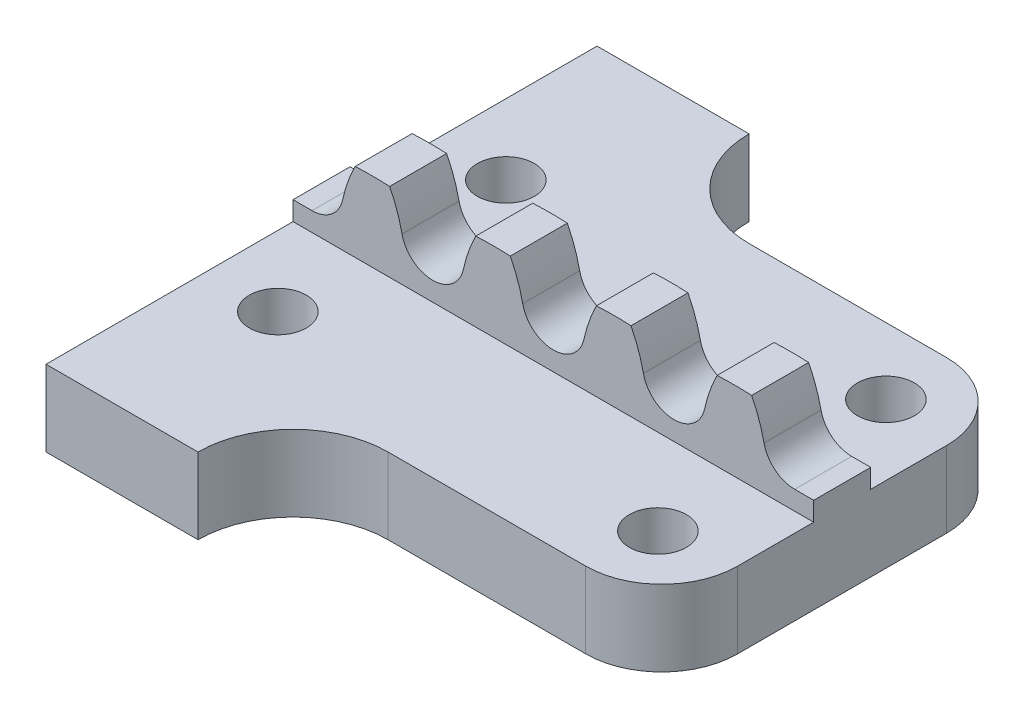
SolidWorks part; units mm, degrees
material "合金钢"
ref_plane "前视基准面" through (0, 0, 0) normal (0, 0, 1) x (1, 0, 0)
ref_plane "上视基准面" through (0, 0, 0) normal (0, 1, 0) x (1, 0, 0)
ref_plane "右视基准面" through (0, 0, 0) normal (1, 0, 0) x (0, 0, -1)
sketch "草图1" plane through (0, 0, 0) normal (0, 0, 1) x (1, 0, 0)
  line L0 (-0.6404, -1.8816) -> (-1.6404, -1.8816)
  line L1 (24.7596, -1.8816) -> (25.7596, -1.8816)
  line L2 (-1.6404, -1.8816) -> (-1.6404, -2.8816)
  line L3 (-1.6404, -2.8816) -> (25.7596, -2.8816)
  line L4 (25.7596, -2.8816) -> (25.7596, -1.8816)
  line L5 (-1.6404, -2.8816) -> (-1.6404, -6.8816)
  line L6 (-1.6404, -6.8816) -> (25.7596, -6.8816)
  line L7 (25.7596, -6.8816) -> (25.7596, -1.8816)
  arc A0 (4.0971, -0.5771) -> (3.4439, 1.2653) centre (-3.2619, -2.1492) ccw
  arc A1 (4.0971, -0.5771) -> (5.4066, -1.8535) centre (5.7096, -0.2326) ccw
  arc A2 (0.9722, -0.5771) -> (1.6254, 1.2653) centre (8.3312, -2.1492) cw
  arc A3 (0.9722, -0.5771) -> (-0.3374, -1.8535) centre (-0.6404, -0.2326) cw
  arc A4 (3.4439, 1.2653) -> (1.6254, 1.2653) centre (2.5346, -17.2174) ccw
  arc A5 (10.4471, -0.5771) -> (9.7939, 1.2653) centre (3.0881, -2.1492) ccw
  arc A6 (10.4471, -0.5771) -> (11.7566, -1.8535) centre (12.0596, -0.2326) ccw
  arc A7 (7.3222, -0.5771) -> (7.9754, 1.2653) centre (14.6812, -2.1492) cw
  arc A8 (7.3222, -0.5771) -> (6.0126, -1.8535) centre (5.7096, -0.2326) cw
  arc A9 (9.7939, 1.2653) -> (7.9754, 1.2653) centre (8.8846, -17.2174) ccw
  arc A10 (16.7971, -0.5771) -> (16.1439, 1.2653) centre (9.4381, -2.1492) ccw
  arc A11 (16.7971, -0.5771) -> (18.1066, -1.8535) centre (18.4096, -0.2326) ccw
  arc A12 (13.6722, -0.5771) -> (14.3254, 1.2653) centre (21.0312, -2.1492) cw
  arc A13 (13.6722, -0.5771) -> (12.3626, -1.8535) centre (12.0596, -0.2326) cw
  arc A14 (16.1439, 1.2653) -> (14.3254, 1.2653) centre (15.2346, -17.2174) ccw
  arc A15 (23.1471, -0.5771) -> (22.4939, 1.2653) centre (15.7881, -2.1492) ccw
  arc A16 (23.1471, -0.5771) -> (24.4566, -1.8535) centre (24.7596, -0.2326) ccw
  arc A17 (20.0222, -0.5771) -> (20.6754, 1.2653) centre (27.3812, -2.1492) cw
  arc A18 (20.0222, -0.5771) -> (18.7126, -1.8535) centre (18.4096, -0.2326) cw
  arc A19 (22.4939, 1.2653) -> (20.6754, 1.2653) centre (21.5846, -17.2174) ccw
  arc A20 (6.0126, -1.8535) -> (5.4066, -1.8535) centre (5.7096, -0.2326) cw
  arc A21 (12.3626, -1.8535) -> (11.7566, -1.8535) centre (12.0596, -0.2326) cw
  arc A22 (18.1066, -1.8535) -> (18.7126, -1.8535) centre (18.4096, -0.2326) ccw
  arc A23 (-0.6404, -1.8816) -> (0.9722, -0.5771) centre (-0.6404, -0.2326) ccw
  arc A24 (23.1471, -0.5771) -> (24.7596, -1.8816) centre (24.7596, -0.2326) ccw
  dimension "D2" = 1
  dimension "D3" = 1
  dimension "D4" = 1
  dimension "D5" = 4
  dimension "D1" = 4
extrude "凸台-拉伸1" add sketch "草图1" along normal blind 3 contours A24 A16 A15 A19 A17 A18 A22 A11 A10 A14 A12 A13 A21 A6 A5 A9 A7 A8 A20 A1 A0 A4 A2 A3 A23 L0 L2 L3 L4 L1 | L6 L7 L3 L5 region at (-0.4626, -2.1505, 0) region at (12.0596, -4.8816, 0)
extrude "凸台-拉伸2" add sketch "草图1<3>" along normal blind 11 contours L6 L7 L3 L5 region at (12.0596, -4.8816, 0)
sketch "草图1<3>" plane through (0, 0, 0) normal (0, 0, 1) x (1, 0, 0) same geometry as "草图1"
extrude "凸台-拉伸3" add sketch "草图1<4>" against normal blind 8 contours L6 L7 L3 L5 region at (12.0596, -4.8816, 0)
sketch "草图1<4>" plane through (0, 0, 0) normal (0, 0, 1) x (1, 0, 0) same geometry as "草图1"
sketch "草图2" plane through (0, -2.8816, 0) normal (0, 1, 0) x (1, 0, 0)
  line L0 (12.0596, 8) -> (12.0596, -11) construction
  line L1 (-1.6404, 8) -> (25.7596, 8) construction
  line L2 (-1.6404, -11) -> (25.7596, -11) construction
  line L4 (2.0596, -7.5) -> (22.0596, -7.5) construction
  line L5 (2.0596, -7.5) -> (2.0596, 4.5) construction
  line L6 (2.0596, 4.5) -> (22.0596, 4.5) construction
  line L7 (22.0596, -7.5) -> (22.0596, 4.5) construction
  line L8 (2.0596, -7.5) -> (22.0596, 4.5) construction
  line L9 (2.0596, 4.5) -> (22.0596, -7.5) construction
  circle A0 centre (2.0596, 4.5) radius 1.5
  circle A1 centre (22.0596, 4.5) radius 1.5
  circle A2 centre (22.0596, -7.5) radius 1.5
  circle A3 centre (2.0596, -7.5) radius 1.5
  point P6 (12.0596, -1.5)
  dimension "D3" = 3
  dimension "D4" = 3
  dimension "D5" = 3
  dimension "D6" = 3
  dimension "D1" = 12
  dimension "D2" = 20
extrude "切除-拉伸1" cut sketch "草图2" against normal blind 6.5
fillet "圆角1" radius 4 2 edges at (25.7596, -4.8816, 11) (25.7596, -4.8816, -8)
sketch "草图4" plane through (0, 0, -8) normal (0, 0, -1) x (-1, 0, 0)
  line L0 (-10.0596, -6.8816) -> (-10.0596, -11.8816) construction
  line L1 (1.6404, -6.8816) -> (-21.7596, -6.8816) construction
  line L2 (-10.0596, -6.8816) -> (-7.5596, -6.8816) construction
  line L3 (-7.5596, -12.8816) -> (-0.5596, -12.8816) construction
  line L4 (-7.5596, -6.8816) -> (-12.5596, -6.8816)
  line L5 (-7.5596, -6.8816) -> (-7.5596, -12.8816)
  line L7 (-12.5596, -6.8816) -> (-12.5596, -12.8816)
  line L8 (-7.5596, -12.8816) -> (-3.5596, -12.8816) construction
  line L9 (-2.4827, -19.6122) -> (-2.4827, -21.8169)
  arc A0 (-7.5596, -12.8816) -> (-2.4827, -19.6122) centre (-0.5596, -12.8816) ccw
  arc A1 (-12.5596, -12.8816) -> (-2.4827, -21.8169) centre (-3.5596, -12.8816) ccw
  dimension "D1" = 5
  dimension "D2" = 2.5
  dimension "D3" = 6
  dimension "D4" = 5
  dimension "D5" = 7
  dimension "D6" = 9
extrude "凸台-拉伸4" add sketch "草图4" against normal up to surface (19 mm away) up to face at (10.0596, -4.8816, 11)
sketch "草图6" plane through (0, -6.8816, 0) normal (0, -1, 0) x (1, 0, 0)
  line L1 (-2.723, 12.3626) -> (29.5343, 12.3626)
  line L2 (-2.723, 12.3626) -> (-2.723, -11.3462)
  line L3 (-2.723, -11.3462) -> (29.5343, -11.3462)
  line L4 (29.5343, 12.3626) -> (29.5343, -11.3462)
extrude "切除-拉伸2" cut sketch "草图6" along normal blind 21
sketch "草图7" plane through (0, 0, 11) normal (0, 0, 1) x (1, 0, 0)
  line L3 (-1.6404, -2.8816) -> (6.3596, -2.8816)
  line L8 (-1.6404, -2.8816) -> (-1.6404, -6.8816)
  line L9 (-1.6404, -6.8816) -> (6.3596, -6.8816)
  line L10 (6.3596, -2.8816) -> (6.3596, -6.8816)
  point P6 (10.0596, -4.8816)
  dimension "D1" = 4
  dimension "D2" = 8
extrude "凸台-拉伸5" add sketch "草图7" along normal blind 5
sketch "草图8" plane through (0, 0, -8) normal (0, 0, -1) x (-1, 0, 0)
  line L3 (1.6404, -2.8816) -> (-6.3596, -2.8816)
  line L8 (1.6404, -2.8816) -> (1.6404, -6.8816)
  line L9 (1.6404, -6.8816) -> (-6.3596, -6.8816)
  line L10 (-6.3596, -2.8816) -> (-6.3596, -6.8816)
  line L11 (1.6404, -6.8816) -> (-21.7596, -6.8816) construction
  point P6 (-12.0596, -4.8816)
  dimension "D1" = 4
  dimension "D2" = 8
extrude "凸台-拉伸6" add sketch "草图8" along normal blind 5
fillet "圆角2" radius 5 2 edges at (6.3596, -4.8816, 11) (6.3596, -4.8816, -8)
